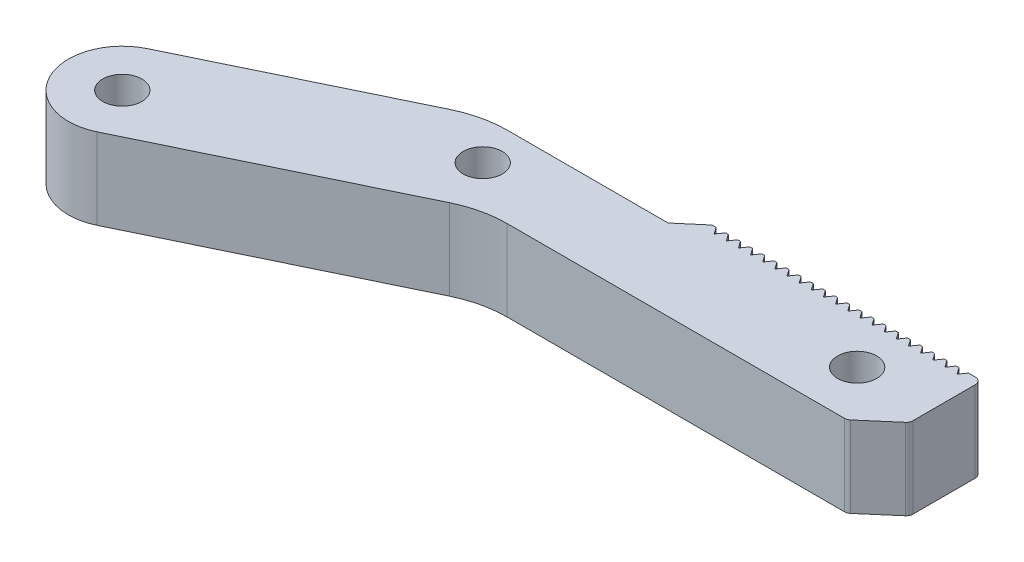
SolidWorks part; units mm, degrees
note: '?' marks a value the reader was unsure of.
ref_plane "Alzado" through (0, 0, 0) normal (0, 0, 1) x (1, 0, 0)
ref_plane "Planta" through (0, 0, 0) normal (0, 1, 0) x (1, 0, 0)
ref_plane "Vista lateral" through (0, 0, 0) normal (1, 0, 0) x (0, 0, -1)
sketch "Croquis1" plane through (0, 0, 0) normal (0, 1, 0) x (1, 0, 0)
  line L83 (5.4912, -22.6523) -> (27.2532, -22.6523) construction
  line L84 (25.9032, -21.6523) -> (25.0032, -21.6523) construction
  line L85 (7.2532, -21.1523) -> (7.2532, -22.6523) construction
  line L86 (27.2532, -21.1523) -> (7.2532, -21.1523) construction
  line L87 (-5.2468, -25.6523) -> (-23.2532, -25.6523) construction
  line L88 (-5.2468, -25.6523) -> (-23.2532, -34.3569) construction
  line L89 (27.2532, -25.6523) -> (-5.2468, -25.6523) construction
  line L90 (24.7532, -28.6523) -> (27.2532, -26.5023)
  line L91 (27.2532, -21.1523) -> (27.2532, -22.6523)
  line L92 (7.2532, -21.1523) -> (5.4912, -22.6523)
  line L93 (7.3532, -21.1523) -> (7.2532, -21.1523)
  line L94 (8.2532, -21.1523) -> (7.9032, -21.6523)
  line L95 (7.5532, -21.1523) -> (7.3532, -21.1523)
  line L96 (7.9032, -21.6523) -> (7.5532, -21.1523)
  line L97 (9.1532, -21.1523) -> (8.8032, -21.6523)
  line L98 (8.4532, -21.1523) -> (8.2532, -21.1523)
  line L99 (8.8032, -21.6523) -> (8.4532, -21.1523)
  line L100 (10.0532, -21.1523) -> (9.7032, -21.6523)
  line L101 (9.3532, -21.1523) -> (9.1532, -21.1523)
  line L102 (9.7032, -21.6523) -> (9.3532, -21.1523)
  line L103 (10.9532, -21.1523) -> (10.6032, -21.6523)
  line L104 (10.2532, -21.1523) -> (10.0532, -21.1523)
  line L105 (10.6032, -21.6523) -> (10.2532, -21.1523)
  line L106 (11.8532, -21.1523) -> (11.5032, -21.6523)
  line L107 (11.1532, -21.1523) -> (10.9532, -21.1523)
  line L108 (11.5032, -21.6523) -> (11.1532, -21.1523)
  line L109 (12.7532, -21.1523) -> (12.4032, -21.6523)
  line L110 (12.0532, -21.1523) -> (11.8532, -21.1523)
  line L111 (12.4032, -21.6523) -> (12.0532, -21.1523)
  line L112 (13.6532, -21.1523) -> (13.3032, -21.6523)
  line L113 (12.9532, -21.1523) -> (12.7532, -21.1523)
  line L114 (13.3032, -21.6523) -> (12.9532, -21.1523)
  line L115 (14.5532, -21.1523) -> (14.2032, -21.6523)
  line L116 (13.8532, -21.1523) -> (13.6532, -21.1523)
  line L117 (14.2032, -21.6523) -> (13.8532, -21.1523)
  line L118 (15.4532, -21.1523) -> (15.1032, -21.6523)
  line L119 (14.7532, -21.1523) -> (14.5532, -21.1523)
  line L120 (15.1032, -21.6523) -> (14.7532, -21.1523)
  line L121 (16.3532, -21.1523) -> (16.0032, -21.6523)
  line L122 (15.6532, -21.1523) -> (15.4532, -21.1523)
  line L123 (16.0032, -21.6523) -> (15.6532, -21.1523)
  line L124 (17.2532, -21.1523) -> (16.9032, -21.6523)
  line L125 (16.5532, -21.1523) -> (16.3532, -21.1523)
  line L126 (16.9032, -21.6523) -> (16.5532, -21.1523)
  line L127 (18.1532, -21.1523) -> (17.8032, -21.6523)
  line L128 (17.4532, -21.1523) -> (17.2532, -21.1523)
  line L129 (17.8032, -21.6523) -> (17.4532, -21.1523)
  line L130 (19.0532, -21.1523) -> (18.7032, -21.6523)
  line L131 (18.3532, -21.1523) -> (18.1532, -21.1523)
  line L132 (18.7032, -21.6523) -> (18.3532, -21.1523)
  line L133 (19.9532, -21.1523) -> (19.6032, -21.6523)
  line L134 (19.2532, -21.1523) -> (19.0532, -21.1523)
  line L135 (19.6032, -21.6523) -> (19.2532, -21.1523)
  line L136 (20.8532, -21.1523) -> (20.5032, -21.6523)
  line L137 (20.1532, -21.1523) -> (19.9532, -21.1523)
  line L138 (20.5032, -21.6523) -> (20.1532, -21.1523)
  line L139 (21.7532, -21.1523) -> (21.4032, -21.6523)
  line L140 (21.0532, -21.1523) -> (20.8532, -21.1523)
  line L141 (21.4032, -21.6523) -> (21.0532, -21.1523)
  line L142 (22.6532, -21.1523) -> (22.3032, -21.6523)
  line L143 (21.9532, -21.1523) -> (21.7532, -21.1523)
  line L144 (22.3032, -21.6523) -> (21.9532, -21.1523)
  line L145 (23.5532, -21.1523) -> (23.2032, -21.6523)
  line L146 (22.8532, -21.1523) -> (22.6532, -21.1523)
  line L147 (23.2032, -21.6523) -> (22.8532, -21.1523)
  line L148 (24.4532, -21.1523) -> (24.1032, -21.6523)
  line L149 (23.7532, -21.1523) -> (23.5532, -21.1523)
  line L150 (24.1032, -21.6523) -> (23.7532, -21.1523)
  line L151 (25.3532, -21.1523) -> (25.0032, -21.6523)
  line L152 (24.6532, -21.1523) -> (24.4532, -21.1523)
  line L153 (25.0032, -21.6523) -> (24.6532, -21.1523)
  line L154 (25.5532, -21.1523) -> (25.3532, -21.1523)
  line L155 (26.2532, -21.1523) -> (27.2532, -21.1523)
  line L156 (25.9032, -21.6523) -> (25.5532, -21.1523)
  line L157 (26.2532, -21.1523) -> (25.9032, -21.6523)
  line L158 (27.2532, -22.6523) -> (27.2532, -21.1523)
  line L159 (-5.2468, -22.6523) -> (-8.2315, -22.6523)
  line L160 (-24.9941, -30.7557) -> (-8.2315, -22.6523)
  line L161 (-21.5123, -37.9582) -> (-2.2621, -28.6523)
  line L162 (24.7532, -28.6523) -> (-2.2621, -28.6523)
  line L163 (27.2532, -22.6523) -> (27.2532, -26.5023)
  line L164 (5.4912, -22.6523) -> (-5.2468, -22.6523)
  circle A4 centre (21.7532, -24.9023) radius 1.45
  circle A5 centre (-5.2468, -25.6523) radius 1.45
  circle A6 centre (-23.2532, -34.3569) radius 1.45
  arc A7 (-21.5123, -37.9582) -> (-24.9941, -30.7557) centre (-23.2532, -34.3569) cw
  point P173 (10.9968, -25.6523)
extrude "Saliente-Extruir1" add sketch "Croquis1" along normal blind 6 contours A7 L161 L162 L90 L163 L91 L155 L157 L156 L154 L151 L153 L152 L148 L150 L149 L145 L147 L146 L142 L144 L143 L139 L141 L140 L136 L138 L137 L133 L135 L134 L130 L132 L131 L127 L129 L128 L124 L126 L125 L121 L123 L122 L118 L120 L119 L115 L117 L116 L112 L114
fillet "Redondeo1" radius 0.5 3 edges at (24.7532, 3, 28.6523) (27.2532, 3, 26.5023) (27.2532, 3, 21.1523)
fillet "Redondeo2" radius 8 2 edges at (-2.2621, 3, 28.6523) (-8.2315, 3, 22.6523)
ref_point "rfinger_cf_center"
ref_plane "rfinger_rotation_plain" through (0, 0, 34.3569) normal (0, 0, -1) x (-1, 0, 0)
ref_axis "rfinger_rotation_axis" through (-23.2532, -1.7531, 34.3569) along (0, 1, 0)?
